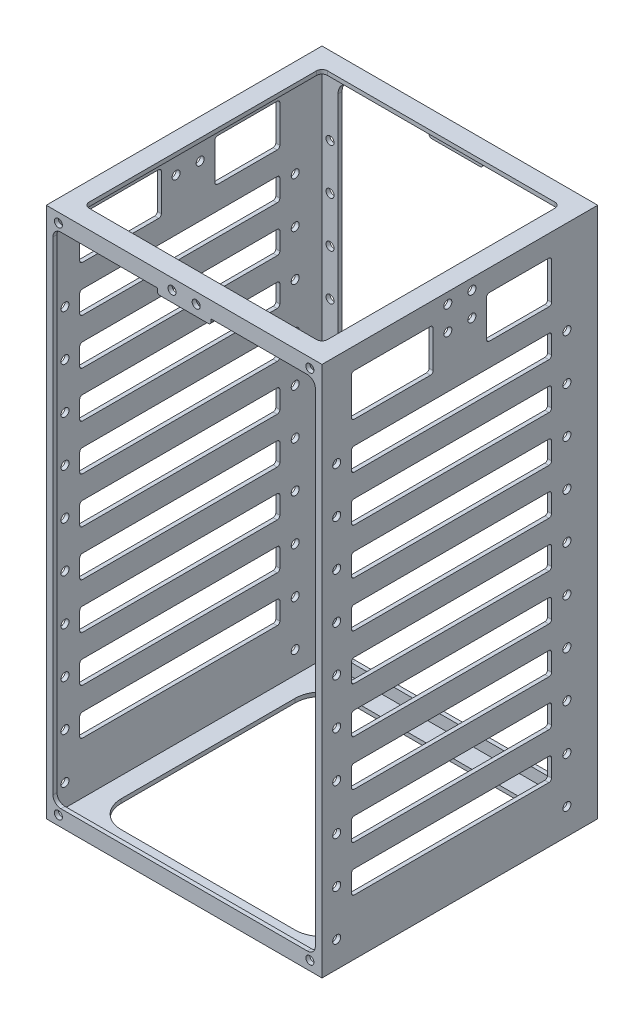
SolidWorks part; units mm, degrees
material "5052-H32"
ref_plane "Front Plane" through (0, 0, 0) normal (0, 0, 1) x (1, 0, 0)
ref_plane "Top Plane" through (0, 0, 0) normal (0, 1, 0) x (1, 0, 0)
ref_plane "Right Plane" through (0, 0, 0) normal (1, 0, 0) x (0, 0, -1)
sketch "Sketch1" plane through (0, 0, 0) normal (0, 1, 0) x (1, 0, 0)
  line L1 (-51.5, -51.5) -> (51.5, -51.5)
  line L2 (-51.5, -51.5) -> (-51.5, 51.5)
  line L3 (-51.5, 51.5) -> (51.5, 51.5)
  line L4 (51.5, -51.5) -> (51.5, 51.5)
  line L5 (-51.5, -51.5) -> (51.5, 51.5) construction
  line L6 (-51.5, 51.5) -> (51.5, -51.5) construction
  line L7 (-32.5, -42.5) -> (32.5, -42.5)
  line L8 (-42.5, -32.5) -> (-42.5, 32.5)
  line L9 (-32.5, 42.5) -> (32.5, 42.5)
  line L10 (42.5, -32.5) -> (42.5, 32.5)
  line L11 (-42.5, -42.5) -> (42.5, 42.5) construction
  line L12 (-42.5, 42.5) -> (42.5, -42.5) construction
  arc A0 (32.5, -42.5) -> (42.5, -32.5) centre (32.5, -32.5) ccw
  arc A1 (32.5, 42.5) -> (42.5, 32.5) centre (32.5, 32.5) cw
  arc A2 (-42.5, 32.5) -> (-32.5, 42.5) centre (-32.5, 32.5) cw
  arc A3 (-32.5, -42.5) -> (-42.5, -32.5) centre (-32.5, -32.5) cw
  point P0 (0, 0)
  point P6 (0, 0)
  dimension "D3" = 10
  dimension "D1" = 103
  dimension "D2" = 42.5
extrude "Boss-Extrude2" add sketch "Sketch1" along normal blind 1.5 contours A3 L7 A0 L10 A1 L9 A2 L8 | L2 L1 L4 L3 region at (0, 0, 0)
sketch "Sketch3" plane through (0, 1.5, 0) normal (0, 1, 0) x (1, 0, 0)
  line L1 (-51.5, -51.5) -> (51.5, -51.5)
  line L2 (-51.5, -51.5) -> (-51.5, 51.5)
  line L3 (-51.5, 51.5) -> (51.5, 51.5)
  line L4 (51.5, -51.5) -> (51.5, 51.5)
  line L5 (-51.5, -51.5) -> (51.5, 51.5) construction
  line L6 (-51.5, 51.5) -> (51.5, -51.5) construction
  line L7 (-50, -50) -> (50, -50)
  line L8 (-50, -50) -> (-50, 50)
  line L9 (-50, 50) -> (50, 50)
  line L10 (50, -50) -> (50, 50)
  line L11 (-50, -50) -> (50, 50) construction
  line L12 (-50, 50) -> (50, -50) construction
  point P0 (0, 0)
  point P7 (0, 0)
  dimension "D1" = 100
extrude "Boss-Extrude3" add sketch "Sketch3" along normal blind 197 contours L8 L7 L10 L9 | L2 L3 L4 L1
sketch "Sketch4" plane through (0, 0, -51.5) normal (0, 0, 1) x (1, 0, 0)
  line L0 (-51.5, 0) -> (51.5, 0) construction
  line L1 (-39, 6) -> (39, 6)
  line L2 (-44, 11) -> (-44, 187.5)
  line L3 (-39, 192.5) -> (39, 192.5)
  line L4 (44, 11) -> (44, 187.5)
  line L5 (-44, 6) -> (44, 192.5) construction
  line L6 (-44, 192.5) -> (44, 6) construction
  line L7 (51.5, 198.5) -> (51.5, 0) construction
  line L8 (-50, 198.5) -> (50, 198.5) construction
  line L9 (-51.5, 198.5) -> (-51.5, 0) construction
  arc A0 (-39, 6) -> (-44, 11) centre (-39, 11) cw
  arc A1 (39, 6) -> (44, 11) centre (39, 11) ccw
  arc A2 (39, 192.5) -> (44, 187.5) centre (39, 187.5) cw
  arc A3 (-44, 187.5) -> (-39, 192.5) centre (-39, 187.5) cw
  point P0 (0, 99.25)
  dimension "D5" = 5
  dimension "D1" = 6
  dimension "D2" = 7.5
  dimension "D3" = 6
  dimension "D4" = 7.5
extrude "Cut-Extrude1" cut sketch "Sketch4" along normal up to surface (1.5 mm away) up to face at (0, 100, -50)
sketch "Sketch5" plane through (0, 0, 51.5) normal (0, 0, 1) x (1, 0, 0)
  line L0 (-51.5, 198.5) -> (51.5, 198.5) construction
  line L1 (-46, 6) -> (46, 6)
  line L2 (-49, 9) -> (-49, 189.5)
  line L3 (-46, 192.5) -> (46, 192.5)
  line L4 (49, 9) -> (49, 189.5)
  line L5 (-49, 6) -> (49, 192.5) construction
  line L6 (-49, 192.5) -> (49, 6) construction
  line L7 (-51.5, 1.5) -> (51.5, 1.5) construction
  line L8 (-51.5, 198.5) -> (-51.5, 0) construction
  line L9 (51.5, 198.5) -> (51.5, 0) construction
  arc A0 (46, 6) -> (49, 9) centre (46, 9) ccw
  arc A1 (-46, 6) -> (-49, 9) centre (-46, 9) cw
  arc A2 (46, 192.5) -> (49, 189.5) centre (46, 189.5) cw
  arc A3 (-49, 189.5) -> (-46, 192.5) centre (-46, 189.5) cw
  point P0 (0, 99.25)
  dimension "D5" = 3
  dimension "D1" = 6
  dimension "D2" = 4.5
  dimension "D3" = 2.5
  dimension "D4" = 2.5
sketch "Sketch6" plane through (51.5, 0, 0) normal (1, 0, 0) x (0, 0, -1)
  line L0 (-51.5, 6) -> (-51.5, 192.5) construction
  line L2 (-51.5, 0) -> (51.5, 0) construction
  circle A0 centre (-46, 9.75) radius 1.5
  circle A1 centre (40, 9.75) radius 1.5
  circle A2 centre (-46, 26.85) radius 1.5
  circle A3 centre (40, 26.85) radius 1.5
  circle A4 centre (-46, 43.95) radius 1.5
  circle A5 centre (40, 43.95) radius 1.5
  circle A6 centre (-46, 61.05) radius 1.5
  circle A7 centre (40, 61.05) radius 1.5
  circle A8 centre (-46, 78.15) radius 1.5
  circle A9 centre (40, 78.15) radius 1.5
  circle A10 centre (-46, 95.25) radius 1.5
  circle A11 centre (40, 95.25) radius 1.5
  circle A12 centre (-46, 112.35) radius 1.5
  circle A13 centre (40, 112.35) radius 1.5
  circle A14 centre (-46, 129.45) radius 1.5
  circle A15 centre (40, 129.45) radius 1.5
  circle A16 centre (-46, 146.55) radius 1.5
  circle A17 centre (40, 146.55) radius 1.5
  circle A18 centre (-46, 163.65) radius 1.5
  circle A19 centre (40, 163.65) radius 1.5
  dimension "D4" = 3
  dimension "D5" = 3
  dimension "D1" = 5.5
  dimension "D2" = 86
  dimension "D3" = 9.75
  dimension "D7" = 17.1
  dimension "D9" = 17.1
  dimension "D6" = 9
  dimension "D8" = 2
extrude "Cut-Extrude2" cut sketch "Sketch6" against normal through all
extrude "Cut-Extrude3" cut sketch "Sketch5" against normal up to surface (1.5 mm away) up to face at (0, 100, 50)
sketch "Sketch7" plane through (51.5, 0, 0) normal (1, 0, 0) x (0, 0, -1)
  line L0 (-40.5, 38.95) -> (-40.5, 45.45)
  line L1 (-39.5, 20.85) -> (33.25, 20.85)
  line L2 (-40.5, 21.85) -> (-40.5, 28.35)
  line L3 (-39.5, 29.35) -> (33.25, 29.35)
  line L4 (34.25, 21.85) -> (34.25, 28.35)
  line L5 (-40.5, 20.85) -> (34.25, 29.35) construction
  line L6 (-40.5, 29.35) -> (34.25, 20.85) construction
  line L7 (-40.5, 158.65) -> (-40.5, 165.15)
  line L8 (-39.5, 37.95) -> (33.25, 37.95)
  line L9 (34.25, 38.95) -> (34.25, 45.45)
  line L10 (-39.5, 46.45) -> (33.25, 46.45)
  line L11 (-40.5, 56.05) -> (-40.5, 62.55)
  line L12 (-39.5, 55.05) -> (33.25, 55.05)
  line L13 (34.25, 56.05) -> (34.25, 62.55)
  line L14 (-39.5, 63.55) -> (33.25, 63.55)
  line L15 (-40.5, 73.15) -> (-40.5, 79.65)
  line L16 (-39.5, 72.15) -> (33.25, 72.15)
  line L17 (34.25, 73.15) -> (34.25, 79.65)
  line L18 (-39.5, 80.65) -> (33.25, 80.65)
  line L19 (-40.5, 90.25) -> (-40.5, 96.75)
  line L20 (-39.5, 89.25) -> (33.25, 89.25)
  line L21 (34.25, 90.25) -> (34.25, 96.75)
  line L22 (-39.5, 97.75) -> (33.25, 97.75)
  line L23 (-40.5, 107.35) -> (-40.5, 113.85)
  line L24 (-39.5, 106.35) -> (33.25, 106.35)
  line L25 (34.25, 107.35) -> (34.25, 113.85)
  line L26 (-39.5, 114.85) -> (33.25, 114.85)
  line L27 (-40.5, 124.45) -> (-40.5, 130.95)
  line L28 (-39.5, 123.45) -> (33.25, 123.45)
  line L29 (34.25, 124.45) -> (34.25, 130.95)
  line L30 (-39.5, 131.95) -> (33.25, 131.95)
  line L31 (-40.5, 141.55) -> (-40.5, 148.05)
  line L32 (-39.5, 140.55) -> (33.25, 140.55)
  line L33 (34.25, 141.55) -> (34.25, 148.05)
  line L34 (-39.5, 149.05) -> (33.25, 149.05)
  line L35 (-39.5, 157.65) -> (33.25, 157.65)
  line L36 (34.25, 158.65) -> (34.25, 165.15)
  line L37 (-39.5, 166.15) -> (33.25, 166.15)
  line L38 (-40.5, 141.55) -> (-40.5, 158.65) construction
  circle A0 centre (-46, 9.75) radius 1.5 construction
  arc A1 (33.25, 29.35) -> (34.25, 28.35) centre (33.25, 28.35) cw
  arc A2 (33.25, 20.85) -> (34.25, 21.85) centre (33.25, 21.85) ccw
  arc A3 (-39.5, 20.85) -> (-40.5, 21.85) centre (-39.5, 21.85) cw
  arc A4 (-40.5, 28.35) -> (-39.5, 29.35) centre (-39.5, 28.35) cw
  arc A5 (-40.5, 45.45) -> (-39.5, 46.45) centre (-39.5, 45.45) cw
  arc A6 (-39.5, 37.95) -> (-40.5, 38.95) centre (-39.5, 38.95) cw
  arc A7 (33.25, 37.95) -> (34.25, 38.95) centre (33.25, 38.95) ccw
  arc A8 (33.25, 46.45) -> (34.25, 45.45) centre (33.25, 45.45) cw
  arc A9 (-40.5, 62.55) -> (-39.5, 63.55) centre (-39.5, 62.55) cw
  arc A10 (-39.5, 55.05) -> (-40.5, 56.05) centre (-39.5, 56.05) cw
  arc A11 (33.25, 55.05) -> (34.25, 56.05) centre (33.25, 56.05) ccw
  arc A12 (33.25, 63.55) -> (34.25, 62.55) centre (33.25, 62.55) cw
  arc A13 (-40.5, 79.65) -> (-39.5, 80.65) centre (-39.5, 79.65) cw
  arc A14 (-39.5, 72.15) -> (-40.5, 73.15) centre (-39.5, 73.15) cw
  arc A15 (33.25, 72.15) -> (34.25, 73.15) centre (33.25, 73.15) ccw
  arc A16 (33.25, 80.65) -> (34.25, 79.65) centre (33.25, 79.65) cw
  arc A17 (-40.5, 96.75) -> (-39.5, 97.75) centre (-39.5, 96.75) cw
  arc A18 (-39.5, 89.25) -> (-40.5, 90.25) centre (-39.5, 90.25) cw
  arc A19 (33.25, 89.25) -> (34.25, 90.25) centre (33.25, 90.25) ccw
  arc A20 (33.25, 97.75) -> (34.25, 96.75) centre (33.25, 96.75) cw
  arc A21 (-40.5, 113.85) -> (-39.5, 114.85) centre (-39.5, 113.85) cw
  arc A22 (-39.5, 106.35) -> (-40.5, 107.35) centre (-39.5, 107.35) cw
  arc A23 (33.25, 106.35) -> (34.25, 107.35) centre (33.25, 107.35) ccw
  arc A24 (33.25, 114.85) -> (34.25, 113.85) centre (33.25, 113.85) cw
  arc A25 (-40.5, 130.95) -> (-39.5, 131.95) centre (-39.5, 130.95) cw
  arc A26 (-39.5, 123.45) -> (-40.5, 124.45) centre (-39.5, 124.45) cw
  arc A27 (33.25, 123.45) -> (34.25, 124.45) centre (33.25, 124.45) ccw
  arc A28 (33.25, 131.95) -> (34.25, 130.95) centre (33.25, 130.95) cw
  arc A29 (-40.5, 148.05) -> (-39.5, 149.05) centre (-39.5, 148.05) cw
  arc A30 (-39.5, 140.55) -> (-40.5, 141.55) centre (-39.5, 141.55) cw
  arc A31 (33.25, 140.55) -> (34.25, 141.55) centre (33.25, 141.55) ccw
  arc A32 (33.25, 149.05) -> (34.25, 148.05) centre (33.25, 148.05) cw
  arc A33 (-40.5, 165.15) -> (-39.5, 166.15) centre (-39.5, 165.15) cw
  arc A34 (-39.5, 157.65) -> (-40.5, 158.65) centre (-39.5, 158.65) cw
  circle A35 centre (40, 9.75) radius 1.5 construction
  arc A36 (33.25, 157.65) -> (34.25, 158.65) centre (33.25, 158.65) ccw
  arc A37 (33.25, 166.15) -> (34.25, 165.15) centre (33.25, 165.15) cw
  point P0 (-3.125, 25.1)
  dimension "D5" = 1
  dimension "D3" = 5.75
  dimension "D1" = 8.5
  dimension "D2" = 11.1
  dimension "D4" = 5.5
  dimension "D7" = 8.6
  dimension "D9" = 8.6
  dimension "D6" = 8
  dimension "D8" = 2
extrude "Cut-Extrude4" cut sketch "Sketch7" against normal through all
sketch "Sketch8" plane through (51.5, 0, 0) normal (1, 0, 0) x (0, 0, -1)
  line L7 (-51.5, 198.5) -> (51.5, 198.5) construction
  line L15 (-39.5, 190.5) -> (33.25, 190.5)
  line L16 (-40.5, 189.5) -> (-40.5, 175.75)
  line L17 (-39.5, 174.75) -> (33.25, 174.75)
  line L18 (34.25, 189.5) -> (34.25, 175.75)
  line L19 (33.25, 166.15) -> (-39.5, 166.15) construction
  arc A15 (33.25, 190.5) -> (34.25, 189.5) centre (33.25, 189.5) cw
  arc A16 (33.25, 174.75) -> (34.25, 175.75) centre (33.25, 175.75) ccw
  arc A17 (-40.5, 175.75) -> (-39.5, 174.75) centre (-39.5, 175.75) ccw
  arc A18 (-39.5, 190.5) -> (-40.5, 189.5) centre (-39.5, 189.5) ccw
  circle A19 centre (-46, 163.65) radius 1.5 construction
  circle A20 centre (40, 163.65) radius 1.5 construction
  point P0 (-2.625, 162.85)
  dimension "D6" = 1
  dimension "D2" = 8.6
  dimension "D8" = 8
  dimension "D9" = 5.5
  dimension "D10" = 5.75
extrude "Cut-Extrude5" cut sketch "Sketch8" against normal through all
sketch "Sketch15" plane through (51.5, 0, 0) normal (1, 0, 0) x (0, 0, -1)
  line L0 (-50, 198.5) -> (-50, 1.5) construction
  line L7 (33.25, 190.5) -> (-39.5, 190.5) construction
  line L8 (-10, 190.5) -> (10, 190.5)
  line L9 (-10, 190.5) -> (-10, 174.75)
  line L10 (-10, 174.75) -> (10, 174.75)
  line L11 (10, 190.5) -> (10, 174.75)
  line L12 (-39.5, 174.75) -> (33.25, 174.75) construction
  dimension "D1" = 20
  dimension "D2" = 40
extrude "Boss-Extrude4" add sketch "Sketch15" against normal up to surface (1.5 mm away) up to face at (50, 182.625, 3.125)
sketch "Sketch16" plane through (-51.5, 0, 0) normal (-1, 0, 0) x (0, 0, 1)
  line L7 (-10, 190.5) -> (10, 190.5)
  line L8 (-10, 190.5) -> (-10, 174.75)
  line L9 (-10, 174.75) -> (10, 174.75)
  line L10 (10, 190.5) -> (10, 174.75)
extrude "Boss-Extrude5" add sketch "Sketch16" against normal up to surface (1.5 mm away) up to face at (-50, 182.625, 3.125)
sketch "Sketch9" plane through (51.5, 0, 0) normal (1, 0, 0) x (0, 0, -1)
  line L0 (-51.5, 198.5) -> (51.5, 198.5) construction
  line L2 (-11.0428, 190) -> (9.2919, 190) construction
  line L3 (-50, 198.5) -> (-50, 1.5) construction
  circle A0 centre (-4.5, 194.5) radius 1.5
  circle A1 centre (4.5, 194.5) radius 1.5
  circle A2 centre (4.5, 185.5) radius 1.5
  circle A3 centre (-4.5, 185.5) radius 1.5
  dimension "D1" = 3
  dimension "D3" = 9
  dimension "D5" = 3
  dimension "D2" = 4
  dimension "D4" = 45.5
  dimension "D6" = 4.5
extrude "Cut-Extrude6" cut sketch "Sketch9" against normal through all
fillet "Fillet1" radius 1 8 edges at (-50.75, 174.75, 10) (-50.75, 190.5, 10) (-50.75, 190.5, -10) (-50.75, 174.75, -10) (50.75, 190.5, 10) (50.75, 174.75, 10) (50.75, 174.75, -10) (50.75, 190.5, -10)
sketch "Sketch18" plane through (0, 0, -51.5) normal (0, 0, -1) x (-1, 0, 0)
  line L0 (-39, 192.5) -> (39, 192.5) construction
  line L1 (-10, 192.5) -> (10, 192.5)
  line L2 (-10, 192.5) -> (-10, 191.5)
  line L3 (-9, 190.5) -> (9, 190.5)
  line L4 (10, 192.5) -> (10, 191.5)
  line L6 (-50, 198.5) -> (-50, 1.5) construction
  arc A0 (9, 190.5) -> (10, 191.5) centre (9, 191.5) ccw
  arc A1 (-10, 191.5) -> (-9, 190.5) centre (-9, 191.5) ccw
  point P4 (-10, 192)
  dimension "D3" = 1
  dimension "D1" = 2
  dimension "D2" = 20
  dimension "D4" = 40
extrude "Boss-Extrude7" add sketch "Sketch18" against normal up to surface (1.5 mm away) up to face at (0, 99.25, -50)
sketch "Sketch17" plane through (0, 0, 51.5) normal (0, 0, 1) x (1, 0, 0)
  line L0 (46, 192.5) -> (-46, 192.5) construction
  line L1 (-10, 192.5) -> (10, 192.5)
  line L2 (-10, 192.5) -> (-10, 191.5)
  line L3 (-9, 190.5) -> (9, 190.5)
  line L4 (10, 192.5) -> (10, 191.5)
  line L5 (-50, 198.5) -> (-50, 1.5) construction
  arc A0 (9, 190.5) -> (10, 191.5) centre (9, 191.5) ccw
  arc A1 (-10, 191.5) -> (-9, 190.5) centre (-9, 191.5) ccw
  dimension "D4" = 1
  dimension "D1" = 20
  dimension "D2" = 40
  dimension "D3" = 2
extrude "Boss-Extrude6" add sketch "Sketch17" against normal up to surface (1.5 mm away) up to face at (0, 99.25, 50)
sketch "Sketch19" plane through (0, 0, 51.5) normal (0, 0, 1) x (1, 0, 0)
  line L0 (0, 198.5) -> (0, 190.5) construction
  line L1 (-9, 190.5) -> (9, 190.5) construction
  line L3 (-51.5, 198.5) -> (51.5, 198.5) construction
  circle A0 centre (-4.5, 194.5) radius 1.5
  circle A1 centre (4.5, 194.5) radius 1.5
  dimension "D1" = 3
  dimension "D2" = 4
  dimension "D3" = 4.5
extrude "Cut-Extrude7" cut sketch "Sketch19" against normal through all
sketch "Sketch20" plane through (0, 0, 51.5) normal (0, 0, 1) x (1, 0, 0)
  line L1 (-51.5, 0) -> (51.5, 0) construction
  line L2 (0, 198.5) -> (0, 0) construction
  line L3 (-51.5, 198.5) -> (51.5, 198.5) construction
  line L4 (-50, 198.5) -> (-50, 1.5) construction
  line L5 (-50, 198.5) -> (-50, 1.5) construction
  circle A0 centre (-46.98, 3.5) radius 1.5
  circle A1 centre (-46.98, 195) radius 1.5
  circle A2 centre (46.98, 3.5) radius 1.5
  circle A3 centre (46.98, 195) radius 1.5
  dimension "D1" = 3
  dimension "D4" = 3
  dimension "D2" = 3.02
  dimension "D3" = 3.5
  dimension "D5" = 3.02
  dimension "D6" = 3.5
extrude "Cut-Extrude8" cut sketch "Sketch20" against normal up to surface (1.5 mm away) up to face at (-6, 194.5, 50)
sketch "Sketch23" plane through (0, 0, -51.5) normal (0, 0, -1) x (-1, 0, 0)
  line L0 (-51.5, 198.5) -> (-51.5, 0) construction
  line L1 (51.5, 0) -> (-51.5, 0) construction
  line L2 (0, 198.5) -> (0, 0) construction
  line L3 (51.5, 198.5) -> (-51.5, 198.5) construction
  circle A0 centre (-47, 17.05) radius 1.5
  circle A2 centre (-47, 34.15) radius 1.5
  circle A3 centre (-47, 51.25) radius 1.5
  circle A4 centre (-47, 68.35) radius 1.5
  circle A5 centre (-47, 85.45) radius 1.5
  circle A6 centre (-47, 102.55) radius 1.5
  circle A7 centre (-47, 119.65) radius 1.5
  circle A8 centre (-47, 136.75) radius 1.5
  circle A9 centre (-47, 153.85) radius 1.5
  circle A10 centre (-47, 170.95) radius 1.5
  circle A11 centre (47, 170.95) radius 1.5
  circle A12 centre (47, 153.85) radius 1.5
  circle A13 centre (47, 136.75) radius 1.5
  circle A14 centre (47, 119.65) radius 1.5
  circle A15 centre (47, 102.55) radius 1.5
  circle A16 centre (47, 85.45) radius 1.5
  circle A17 centre (47, 68.35) radius 1.5
  circle A18 centre (47, 51.25) radius 1.5
  circle A19 centre (47, 34.15) radius 1.5
  circle A20 centre (47, 17.05) radius 1.5
  dimension "D1" = 3
  dimension "D2" = 4.5
  dimension "D3" = 17.05
  dimension "D5" = 17.1
  dimension "D4" = 10
extrude "Cut-Extrude10" cut sketch "Sketch23" against normal up to surface (1.5 mm away) up to face at (-6, 194.5, -50)
sketch "Sketch25" plane through (0, 198.5, 0) normal (0, 1, 0) x (1, 0, 0)
  line L1 (-50, -50) -> (50, -50)
  line L2 (-50, -50) -> (-50, 50)
  line L3 (-50, 50) -> (50, 50)
  line L4 (50, -50) -> (50, 50)
  line L5 (-50, -50) -> (50, 50) construction
  line L6 (-50, 50) -> (50, -50) construction
  point P0 (0, 0)
extrude "Boss-Extrude8" add sketch "Sketch25" against normal blind 1.5
sketch "Sketch26" plane through (0, 198.5, 0) normal (0, 1, 0) x (1, 0, 0)
  line L0 (-51.5, -51.5) -> (-51.5, 51.5) construction
  line L1 (-42.5, -44.5) -> (42.5, -44.5)
  line L2 (-44.5, -42.5) -> (-44.5, 42.5)
  line L3 (-42.5, 44.5) -> (42.5, 44.5)
  line L4 (44.5, -42.5) -> (44.5, 42.5)
  line L5 (-44.5, -44.5) -> (44.5, 44.5) construction
  line L6 (-44.5, 44.5) -> (44.5, -44.5) construction
  arc A0 (-44.5, 42.5) -> (-42.5, 44.5) centre (-42.5, 42.5) cw
  arc A1 (42.5, 44.5) -> (44.5, 42.5) centre (42.5, 42.5) cw
  arc A2 (42.5, -44.5) -> (44.5, -42.5) centre (42.5, -42.5) ccw
  arc A3 (-42.5, -44.5) -> (-44.5, -42.5) centre (-42.5, -42.5) cw
  point P0 (0, 0)
  dimension "D2" = 2
  dimension "D1" = 7
extrude "Cut-Extrude11" cut sketch "Sketch26" against normal up to surface (1.5 mm away) up to face at (0, 197, 0)
